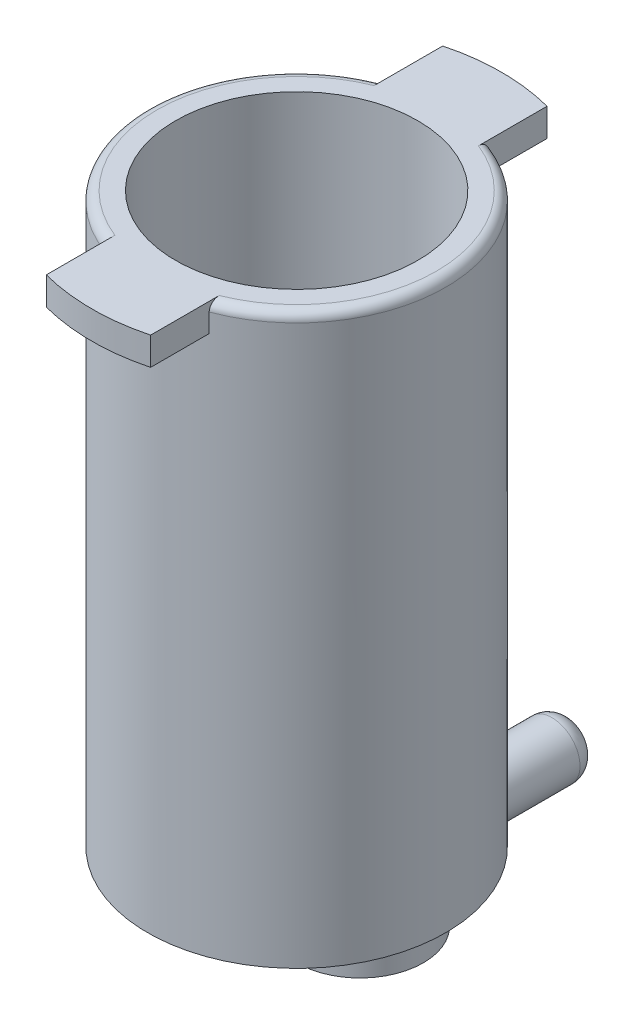
SolidWorks part; units mm, degrees
ref_plane "Front Plane" through (0, 0, 0) normal (0, 0, 1) x (1, 0, 0)
ref_plane "Top Plane" through (0, 0, 0) normal (0, 1, 0) x (1, 0, 0)
ref_plane "Right Plane" through (0, 0, 0) normal (1, 0, 0) x (0, 0, -1)
sketch "Sketch1" plane through (0, 0, 0) normal (0, 1, 0) x (1, 0, 0)
  circle A0 centre (0, 0) radius 8
extrude "Boss-Extrude1" add sketch "Sketch1" along normal blind 30.5
shell "Shell1" thickness 1.5 removed face at (0, 30.5, 8)
sketch "Sketch2" plane through (0, 0, 0) normal (0, -1, 0) x (1, 0, 0)
  circle A0 centre (0, -3.4) radius 3.4
extrude "Boss-Extrude2" add sketch "Sketch2" along normal blind 5.4 contours A0
shell "Shell2" thickness 1.5 removed face at (0, 1.5, 6.5)
sketch "Sketch4" plane through (0, 0, 0) normal (0, -1, 0) x (1, 0, 0)
  line L0 (-3.4, -3.4) -> (3.4, -3.4) construction
  circle A0 centre (0, -3.4) radius 3.4 construction
  circle A1 centre (0, -3.4) radius 3.4 construction
ref_plane "Plane1" through (0, 0, -3.4) normal (0, 0, 1) x (1, 0, 0)
sketch "Sketch5" plane through (0, 0, -3.4) normal (0, 0, 1) x (1, 0, 0)
  line L0 (0, 0) -> (0, -5.4) construction
  line L1 (-3.4, -5.4) -> (3.4, -5.4) construction
  circle A0 centre (0, -2.3538) radius 2.45
extrude "Boss-Extrude5" add sketch "Sketch5" against normal blind 4.9
sketch "Sketch6" plane through (0, 0, -8.3) normal (0, 0, -1) x (-1, 0, 0)
  circle A0 centre (0, -2.3538) radius 1.5
extrude "Boss-Extrude6" add sketch "Sketch6" along normal blind 6.3
sketch "Sketch7" plane through (0, 0, -14.6) normal (0, 0, -1) x (-1, 0, 0)
  circle A0 centre (0, -2.3538) radius 0.95
extrude "Cut-Extrude1" cut sketch "Sketch7" against normal blind 11.3
sketch "Sketch8" plane through (0, -3.9, 0) normal (0, 1, 0) x (1, 0, 0)
  line L0 (-3.4, 3.4) -> (3.4, 3.4) construction
  circle A0 centre (0, 3.4) radius 1.9
extrude "Cut-Extrude2" cut sketch "Sketch8" along normal through all contours A0
fillet "Fillet1" radius 1 1 edges at (-1.5, -2.3538, -14.6)
fillet "Fillet2" radius 0.5 1 edges at (0, 30.5, 8)
sketch "Sketch9" plane through (0, 30.5, 0) normal (0, 1, 0) x (1, 0, 0)
  line L0 (-1.4133, 0) -> (1.7562, 0) construction
  line L1 (2.8, 10.6377) -> (2.8, 5.866)
  line L2 (-2.8, 10.6377) -> (-2.8, 5.866)
  line L3 (-2.8, -10.6377) -> (-2.8, -5.866)
  line L4 (2.8, -10.6377) -> (2.8, -5.866)
  arc A3 (2.8, -10.6377) -> (-2.8, -10.6377) centre (0, 0) cw
  arc A4 (2.8, -5.866) -> (-2.8, -5.866) centre (0, 0) cw
  arc A5 (2.8, 5.866) -> (-2.8, 5.866) centre (0, 0) ccw
  arc A6 (2.8, 10.6377) -> (-2.8, 10.6377) centre (0, 0) ccw
  point P19 (0, 0)
extrude "Boss-Extrude7" add sketch "Sketch9" against normal blind 1.5
mirror "Mirror1" about plane through (0, 0, 0) normal (1, 0, 0) of bodies 107
